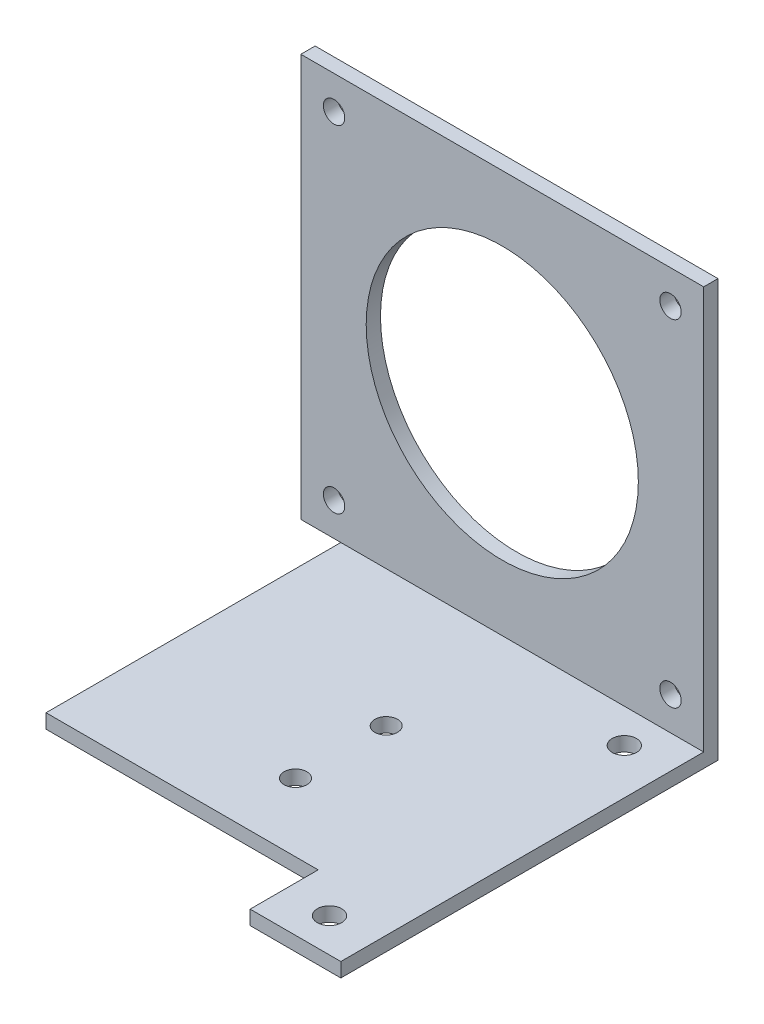
SolidWorks part; units mm, degrees
ref_plane "Front Plane" through (0, 0, 0) normal (0, 0, 1) x (1, 0, 0)
ref_plane "Top Plane" through (0, 0, 0) normal (0, 1, 0) x (1, 0, 0)
ref_plane "Right Plane" through (0, 0, 0) normal (1, 0, 0) x (0, 0, -1)
sketch "Sketch1" plane through (0, 0, 0) normal (0, 1, 0) x (1, 0, 0)
  line L2 (-25.4, 27.4) -> (25.4, 27.4)
  line L3 (25.4, 27.4) -> (25.4, -25.4)
  line L4 (25.4, -25.4) -> (12.7, -25.4)
  line L5 (12.7, -25.4) -> (12.7, -15.875)
  line L6 (12.7, -15.875) -> (-25.4, -15.875)
  line L7 (-25.4, -15.875) -> (-25.4, 27.4)
  line L8 (19.05, 20.6375) -> (19.05, -20.6375) construction
  line L9 (0, 6.35) -> (0, -6.35) construction
  circle A0 centre (19.05, 20.6375) radius 1.7
  circle A1 centre (19.05, -20.6375) radius 1.7
  circle A2 centre (0, 6.35) radius 1.5875
  circle A3 centre (0, -6.35) radius 1.5875
  point P0 (-25.4, 25.4)
  point P8 (0, 0)
  point P18 (0, 0)
  point P19 (-25.4, 31.6123)
  point P24 (0, 0)
  dimension "D5" = 3.4
  dimension "D9" = 3.175
  dimension "D1" = 50.8
  dimension "D2" = 52.8
  dimension "D3" = 12.7
  dimension "D4" = 9.525
  dimension "D6" = 41.275
  dimension "D7" = 6.35
  dimension "D8" = 25.4
  dimension "D10" = 12.7
  dimension "D11" = 9.525
  dimension "D12" = 4.7625
extrude "Boss-Extrude1" add sketch "Sketch1" along normal blind 2
sketch "Sketch2" plane through (0, 2, 0) normal (0, 1, 0) x (1, 0, 0)
  line L0 (25.4, 27.4) -> (25.4, 25.4)
  line L2 (25.4, -25.4) -> (25.4, 27.4) construction
  line L3 (25.4, 25.4) -> (-31, 25.4)
  line L5 (-31, 25.4) -> (-31, 27.4)
  line L6 (-31, 27.4) -> (25.4, 27.4)
  dimension "D1" = 56.4
  dimension "D2" = 2
extrude "Boss-Extrude2" add sketch "Sketch2" along normal blind 56.4
sketch "Sketch3" plane through (0, 0, -27.4) normal (0, 0, -1) x (-1, 0, 0)
  line L0 (-25.4, 58.4) -> (31, 2) construction
  line L1 (31, 58.4) -> (-25.4, 2) construction
  line L2 (-25.4, 58.4) -> (-25.4, 0) construction
  circle A0 centre (2.8, 30.2) radius 19.05
  circle A1 centre (26.35, 53.75) radius 1.5
  circle A2 centre (26.35, 6.65) radius 1.5
  circle A3 centre (-20.75, 6.65) radius 1.5
  circle A4 centre (-20.75, 53.75) radius 1.5
  point P19 (-20.4717, 53.3589)
  point P20 (0, 0)
  point P21 (0, 0)
  point P22 (0, 0)
  dimension "D1" = 3
  dimension "D3" = 38.1
  dimension "D2" = 47.1
extrude "Cut-Extrude1" cut sketch "Sketch3" against normal through all
